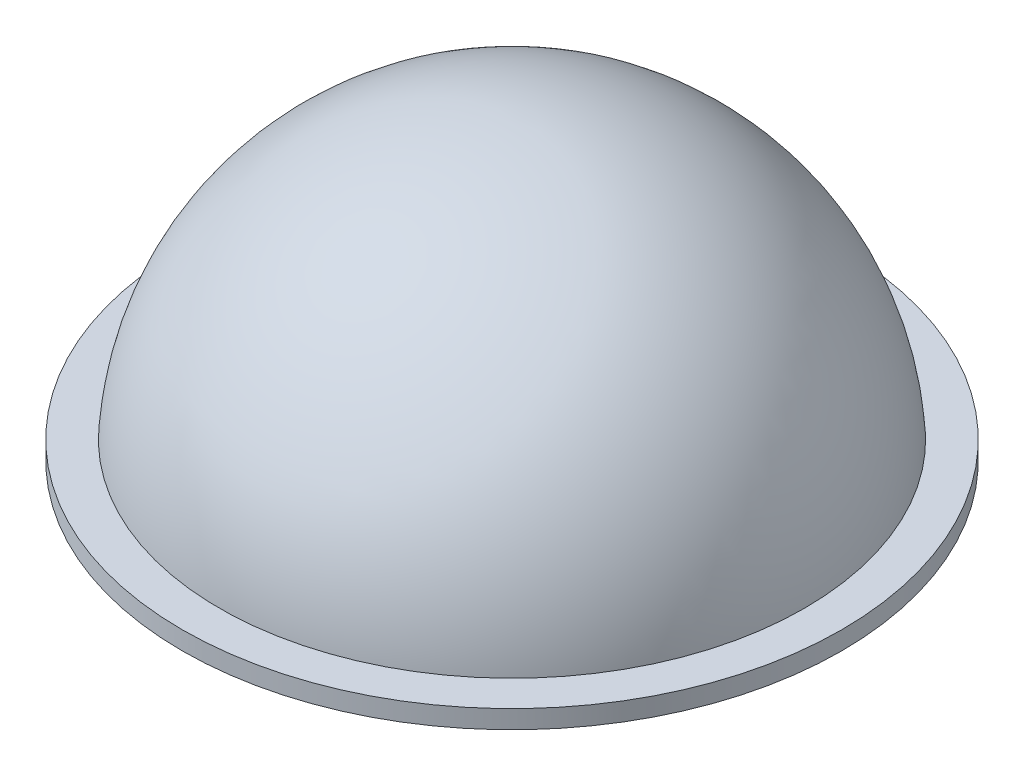
SolidWorks part; units mm, degrees
ref_plane "Front" through (0, 0, 0) normal (0, 0, 1) x (1, 0, 0)
ref_plane "Top" through (0, 0, 0) normal (0, 1, 0) x (1, 0, 0)
ref_plane "Right" through (0, 0, 0) normal (1, 0, 0) x (0, 0, -1)
sketch "Sketch1" plane through (0, 0, 0) normal (0, 0, 1) x (1, 0, 0)
  line L2 (-90, 0) -> (-90, 5)
  line L3 (-90, 5) -> (-79.8436, 5)
  line L8 (0, 0) -> (0, 80) construction
  line L9 (0, 80) -> (0, 75)
  line L10 (-90, 0) -> (80, 0) construction
  line L11 (-90, 0) -> (-75, 0)
  arc A0 (80, 0) -> (-80, 0) centre (0, 0) ccw construction
  arc A1 (0, 75) -> (-75, 0) centre (0, 0) ccw
  arc A2 (-79.8436, 5) -> (0, 80) centre (0, 0) cw
  dimension "D1" = 160
  dimension "D2" = 150
  dimension "D3" = 10
  dimension "D6" = 5
revolve "Revolve1" add sketch "Sketch1" angle 360 about L8
